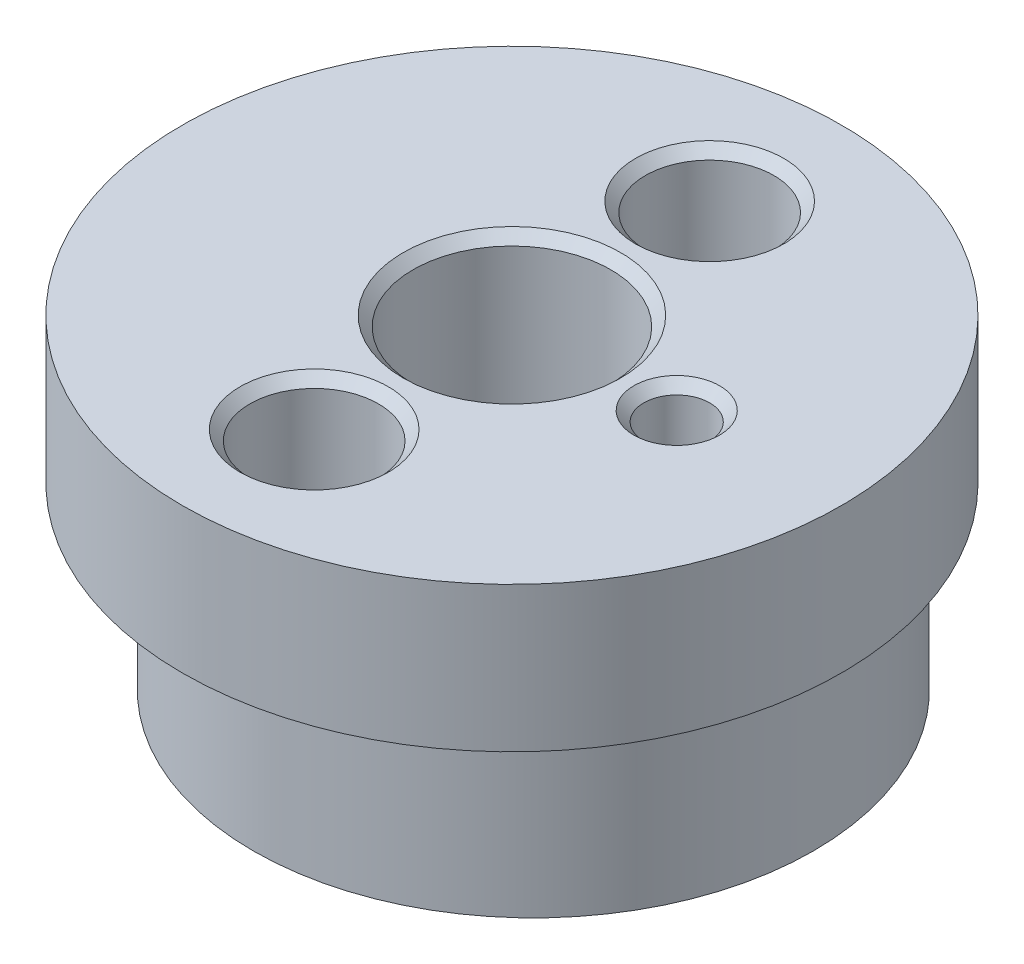
SolidWorks part; units mm, degrees
ref_plane "Front Plane" through (0, 0, 0) normal (0, 0, 1) x (1, 0, 0)
ref_plane "Top Plane" through (0, 0, 0) normal (0, 1, 0) x (1, 0, 0)
ref_plane "Right Plane" through (0, 0, 0) normal (1, 0, 0) x (0, 0, -1)
sketch "Sketch1" plane through (0, 0, 0) normal (0, 1, 0) x (1, 0, 0)
  circle A0 centre (0, 0) radius 8.5
  dimension "D1" = 17
extrude "Boss-Extrude1" add sketch "Sketch1" along normal blind 5.5
sketch "Sketch2" plane through (0, 5.5, 0) normal (0, 1, 0) x (1, 0, 0)
  circle A0 centre (-0.65, 0) radius 10
  dimension "D1" = 20
  dimension "D2" = 0.65
extrude "Boss-Extrude2" add sketch "Sketch2" along normal blind 4 and the other way blind 0.4
sketch "Sketch3" plane through (0, 0, 0) normal (0, -1, 0) x (1, 0, 0)
  circle A0 centre (-0.65, 0) radius 3
  circle A3 centre (-0.65, 0) radius 10 construction
  dimension "D1" = 6
extrude "Cut-Extrude1" cut sketch "Sketch3" against normal through all
sketch "Sketch6" plane through (0, 0, 0) normal (0, -1, 0) x (1, 0, 0)
  line L3 (4.35, 0) -> (0, 0) construction
  circle A0 centre (0, 0) radius 8.5 construction
  circle A2 centre (0, 0) radius 8.5 construction
  circle A4 centre (4.35, 0) radius 1
  dimension "D1" = 2
extrude "Cut-Extrude4" cut sketch "Sketch6" against normal through all contours A4
hole_wizard "Ø3.2 (3.2) Diameter Hole1" positions "Sketch7" profile "Sketch8" hole size "Ø3.2" standard "DIN" end condition up to next
sketch "Sketch7" plane through (0, 0, 0) normal (0, -1, 0) x (-1, 0, 0)
  line L0 (0.65, -6) -> (0.65, 0)
  line L1 (0.65, 0) -> (0.65, 6)
  circle A0 centre (0.65, 0) radius 6
  circle A1 centre (0.65, 0) radius 3 construction
  point P0 (0.65, 6)
  point P2 (0.65, -6)
  dimension "D1" = 12
sketch "Sketch8" plane through (-0.65, 0, -6) normal (1, 0, 0) x (0, 0, -1)
  line L0 (0, 0) -> (0, 9.5)
  line L1 (0, 9.5) -> (1.6, 9.5)
  line L2 (1.6, 9.5) -> (1.6, 0)
  line L5 (1.6, 0) -> (0, 0)
  line L11 (0, -6.35) -> (0, 107.95) construction
  dimension "Thru Hole Dia." = 3.2
  dimension "Thru Hole Depth" = 9.5
sketch "Sketch10" plane through (0, 9.5, 0) normal (0, 1, 0) x (1, 0, 0)
  circle A0 centre (-0.65, 6) radius 1.95
  circle A1 centre (-0.65, -6) radius 1.95
  dimension "D1" = 3.9
extrude "Cut-Extrude5" cut sketch "Sketch10" against normal blind 4
chamfer "Chamfer1" distance 0.3 angle 45 8 edges at (-0.65, 9.5, -4.05) (-0.65, 9.5, 7.95) (-0.65, 0, 4.4) (-0.65, 0, -7.6) (-0.65, 0, -3) (4.35, 0, -1) (-0.65, 9.5, -3) (4.35, 9.5, -1)
